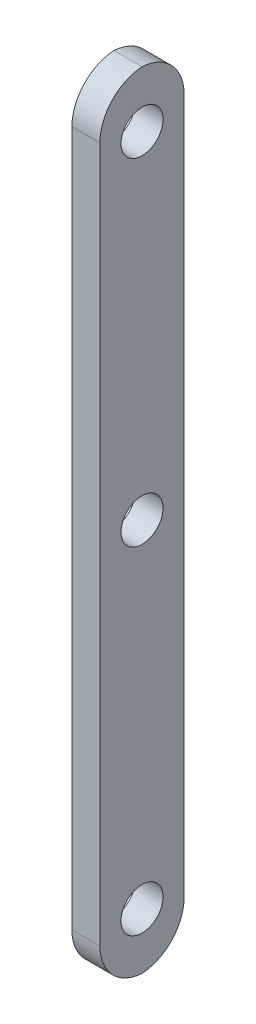
SolidWorks part; units mm, degrees
ref_plane "Front Plane" through (0, 0, 0) normal (0, 0, 1) x (1, 0, 0)
ref_plane "Top Plane" through (0, 0, 0) normal (0, 1, 0) x (1, 0, 0)
ref_plane "Right Plane" through (0, 0, 0) normal (1, 0, 0) x (0, 0, -1)
sketch "Sketch1" plane through (0, 0, 0) normal (1, 0, 0) x (0, 0, -1)
  line L1 (-7.5, -70) -> (7.5, -70)
  line L2 (-7.5, -70) -> (-7.5, 70)
  line L3 (-7.5, 70) -> (7.5, 70)
  line L4 (7.5, -70) -> (7.5, 70)
  line L5 (0, 0) -> (0.2876, 3.739) construction
  line L6 (-0.2876, 3.739) -> (0, 0) construction
  circle A0 centre (0, 0) radius 3.75
  circle A1 centre (0, 60) radius 3.75
  circle A2 centre (0, -60) radius 3.75
  point P0 (0, 0)
  dimension "D3" = 7.5
  dimension "D4" = 7.5
  dimension "D5" = 7.5
  dimension "D1" = 140
  dimension "D2" = 15
  dimension "D6" = 10
  dimension "D7" = 10
  dimension "D8" = 7.5
  dimension "D9" = 7.5
  dimension "D10" = 7.5
  dimension "D11" = 70
extrude "Boss-Extrude1" add sketch "Sketch1" along normal blind 5
fillet "Fillet1" radius 8 4 edges at (2.5, -70, 7.5) (2.5, -70, -7.5) (2.5, 70, -7.5) (2.5, 70, 7.5)
